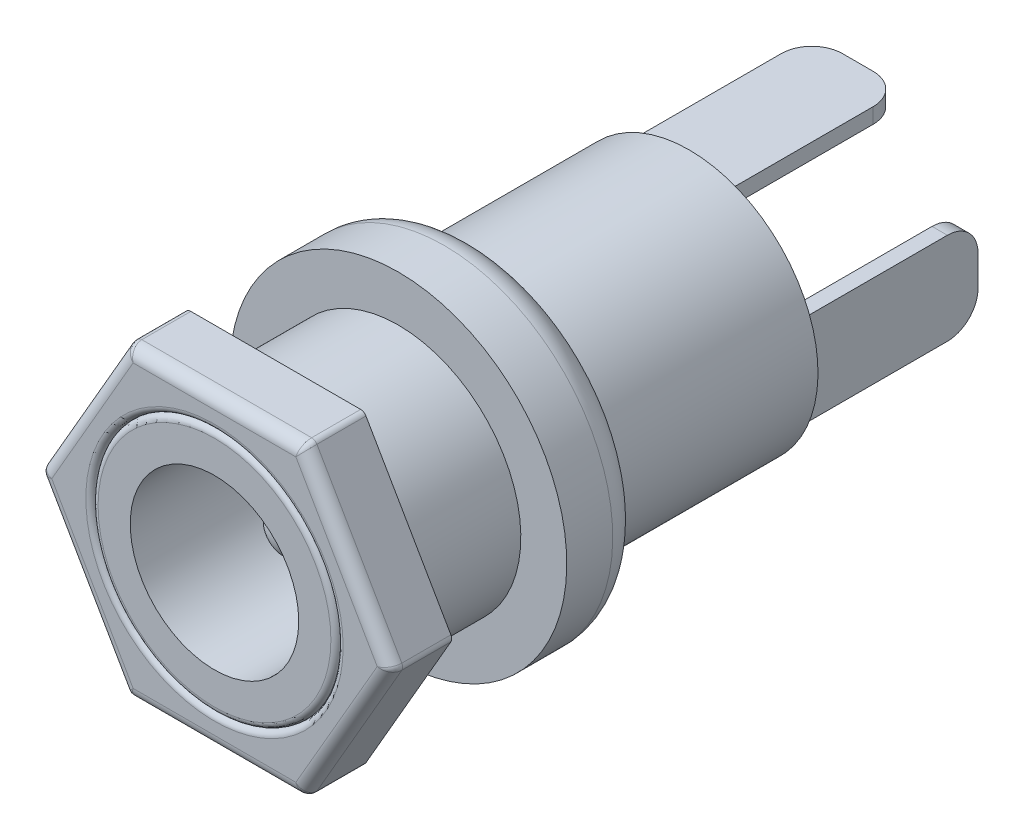
SolidWorks part; units mm, degrees
ref_plane "Спереди" through (0, 0, 0) normal (0, 0, 1) x (1, 0, 0)
ref_plane "Сверху" through (0, 0, 0) normal (0, 1, 0) x (1, 0, 0)
ref_plane "Справа" through (0, 0, 0) normal (1, 0, 0) x (0, 0, -1)
sketch "Эскиз1" plane through (0, 0, 0) normal (1, 0, 0) x (0, 0, -1)
  line L0 (0, 0) -> (0, 4)
  line L1 (0, 4) -> (6, 4)
  line L2 (6, 4) -> (6, 5.5)
  line L3 (6, 5.5) -> (8.5, 5.5)
  line L4 (8.5, 5.5) -> (8.5, 4.2)
  line L5 (8.5, 4.2) -> (15.5, 4.2)
  line L6 (15.5, 4.2) -> (15.5, 0)
  line L7 (15.5, 0) -> (0, 0)
  dimension "D1" = 4
  dimension "D2" = 2.5
  dimension "D3" = 5.5
  dimension "D4" = 4.2
  dimension "D5" = 6
  dimension "D6" = 15.5
revolve "Повернуть1" add sketch "Эскиз1" angle 360 about L7
cosmetic thread "Условное изображение резьбы1" parameters "D2"=6.891
sketch "Эскиз2" plane through (0, 0, -15.5) normal (0, 0, -1) x (-1, 0, 0)
  line L0 (0, 0) -> (0, 4.2) construction
  line L1 (-1.5, 3.923) -> (1.5, 3.923)
  line L2 (-1.5, 3.923) -> (-1.5, 3.423)
  line L3 (-1.5, 3.423) -> (1.5, 3.423)
  line L4 (1.5, 3.923) -> (1.5, 3.423)
  line L5 (-1.5, 3.923) -> (1.5, 3.423) construction
  line L6 (-1.5, 3.423) -> (1.5, 3.923) construction
  line L7 (-3.923, 1.5) -> (-3.423, 1.5)
  line L8 (-3.923, -1.5) -> (-3.923, 1.5)
  line L9 (-3.923, -1.5) -> (-3.423, -1.5)
  line L10 (-3.423, -1.5) -> (-3.423, 1.5)
  line L11 (-1.5, -3.923) -> (-1.5, -3.423)
  line L12 (1.5, -3.923) -> (-1.5, -3.923)
  line L13 (1.5, -3.923) -> (1.5, -3.423)
  line L14 (1.5, -3.423) -> (-1.5, -3.423)
  circle A0 centre (0, 0) radius 4.2 construction
  circle A1 centre (0, 0) radius 4.2 construction
  point P0 (0, 3.673)
  point P23 (0, 0)
  dimension "D1" = 0.5
  dimension "D2" = 3
  dimension "D3" = 3
extrude "Бобышка-Вытянуть1" add sketch "Эскиз2" along normal blind 5.5 separate body
fillet "Скругление1" radius 1 2 edges at (1.5, 3.673, -21) (-1.5, 3.673, -21)
fillet "Скругление2" radius 1 2 edges at (3.673, -1.5, -21) (3.673, 1.5, -21)
fillet "Скругление3" radius 1 2 edges at (-1.5, -3.673, -21) (1.5, -3.673, -21)
fillet "Скругление5" radius 1 1 edges at (0, 5.5, -8.5)
sketch "Эскиз3" plane through (0, 0, 0) normal (0, 0, 1) x (1, 0, 0)
  circle A0 centre (0, 0) radius 2.75
  dimension "D1" = 5.5
extrude "Вырез-Вытянуть1" cut sketch "Эскиз3" against normal blind 11
sketch "Эскиз4" plane through (0, 0, -11) normal (0, 0, 1) x (1, 0, 0)
  circle A0 centre (0, 0) radius 1
  dimension "D1" = 2
extrude "Бобышка-Вытянуть2" add sketch "Эскиз4" along normal blind 9 separate body
fillet "Скругление4" radius 1 1 edges at (1, 0, -2)
sketch "Эскиз5" [suppressed] plane through (0, 0, -11) normal (0, 0, 1) x (1, 0, 0)
  circle A0 centre (0, 0) radius 1.25
  dimension "D1" = 2.5
extrude "Бобышка-Вытянуть3" [suppressed] add sketch "Эскиз5" along normal blind 9 separate body
fillet "Скругление6" [suppressed] radius 1.25
sketch "Эскиз6" plane through (0, 0, 0) normal (0, 0, 1) x (1, 0, 0)
  line L1 (5.7735, 0) -> (2.8868, 5)
  line L2 (2.8868, 5) -> (-2.8868, 5)
  line L3 (-2.8868, 5) -> (-5.7735, 0)
  line L4 (-5.7735, 0) -> (-2.8868, -5)
  line L5 (-2.8868, -5) -> (2.8868, -5)
  line L6 (2.8868, -5) -> (5.7735, 0)
  circle A0 centre (0, 0) radius 5 construction
  circle A1 centre (0, 0) radius 4
  dimension "D1" = 10
extrude "Бобышка-Вытянуть4" add sketch "Эскиз6" against normal blind 2 separate body
fillet "Скругление7" radius 0.2 1 edges at (4, 0, 0)
fillet "Скругление8" radius 0.2 6 edges at (-2.8868, -5, -1) (2.8868, -5, -1) (5.7735, 0, -1) (2.8868, 5, -1) (-2.8868, 5, -1) (-5.7735, 0, -1)
fillet "Скругление9" radius 0.4 12 edges at (-2.8713, 4.9732, 0) (0, 5, 0) (2.8713, 4.9732, 0) (4.3301, 2.5, 0) (5.7426, 0, 0) (4.3301, -2.5, 0) (2.8713, -4.9732, 0) (0, -5, 0) (-2.8713, -4.9732, 0) (-4.3301, -2.5, 0) (-5.7426, 0, 0) (-4.3301, 2.5, 0)
fillet "Скругление10" radius 0.2 1 edges at (0, 4, 0)
